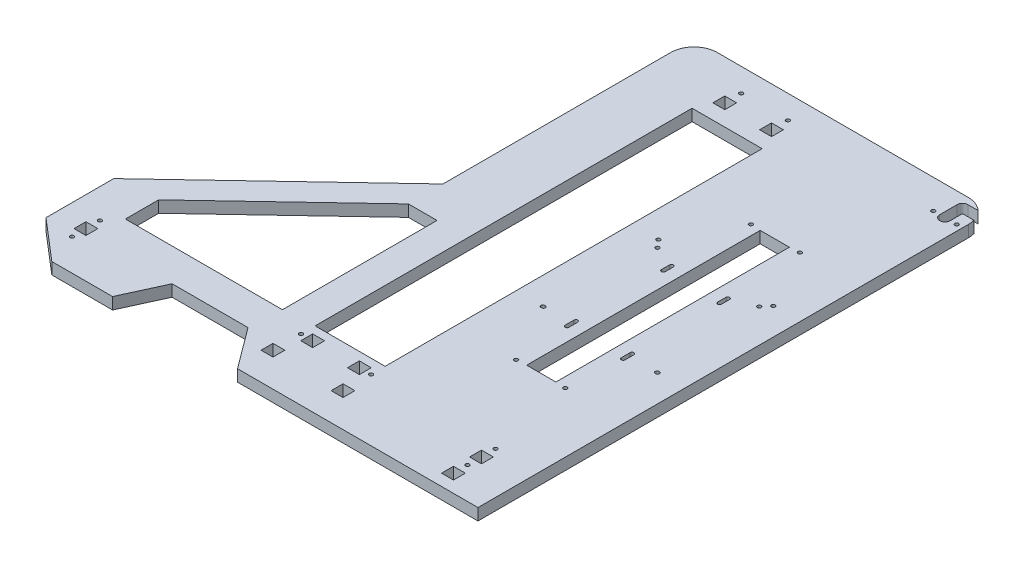
SolidWorks part; units mm, degrees
ref_plane "Front Plane" through (0, 0, 0) normal (0, 0, 1) x (1, 0, 0)
ref_plane "Top Plane" through (0, 0, 0) normal (0, 1, 0) x (1, 0, 0)
ref_plane "Right Plane" through (0, 0, 0) normal (1, 0, 0) x (0, 0, -1)
sketch "Sketch1" plane through (0, 0, 0) normal (0, 1, 0) x (1, 0, 0)
  line L0 (0, 0) -> (-235, 0)
  line L1 (-235, 0) -> (-235, -215)
  line L2 (-235, -215) -> (-380, -352)
  line L3 (-380, -352) -> (-380, -410)
  line L4 (-380, -410) -> (-345, -440)
  line L5 (-345, -440) -> (-293, -440)
  line L6 (-293, -440) -> (-277, -405)
  line L7 (-277, -405) -> (-212, -405)
  line L8 (-212, -405) -> (-185.9255, -440)
  line L9 (-185.9255, -440) -> (0, -440)
  line L10 (0, 0) -> (0, -440)
  line L12 (-293, -440) -> (-185.9255, -440) construction
  dimension "D3" = 235
  dimension "D5" = 58
  dimension "D13" = 190
  dimension "D7" = 35
  dimension "D2" = 126.686
  dimension "D11" = 65
  dimension "D15" = 52
  dimension "D12" = 30
  dimension "D10" = 35
  dimension "D14" = 16
  dimension "D6" = 380
  dimension "D4" = 440
extrude "Boss-Extrude1" add sketch "Sketch1" along normal blind 10
sketch "Sketch16" plane through (0, 10, 0) normal (0, 1, 0) x (1, 0, 0)
  line L0 (0, -440) -> (20, -440)
  line L1 (20, -440) -> (20, 0)
  line L2 (20, 0) -> (0, 0)
  line L3 (0, 0) -> (0, -440)
  dimension "D1" = 20
  dimension "D2" = 90
extrude "Boss-Extrude2" add sketch "Sketch16" against normal through all
sketch "Sketch2" plane through (0, 10, 0) normal (0, 1, 0) x (1, 0, 0)
  line L0 (-235, -215) -> (-235, -405) construction
  line L1 (-277, -405) -> (-212, -405) construction
  line L2 (-345, -440) -> (-345, -318.931) construction
  line L3 (-235, -215) -> (-380, -352) construction
  line L4 (-345, -348.5097) -> (-235, -244.5787)
  line L5 (-235, -244.5787) -> (-210.5, -244.5787)
  line L6 (-210.5, -244.5787) -> (-210.5, -377)
  line L7 (-210.5, -377) -> (-345, -377)
  line L8 (-345, -377) -> (-345, -348.5097)
  line L9 (0, -440) -> (0, 0) construction
  line L10 (-184.5, -375) -> (-124.5, -375)
  line L11 (-184.5, -375) -> (-184.5, -52.1)
  line L12 (-184.5, -52.1) -> (-124.5, -52.1)
  line L13 (-124.5, -375) -> (-124.5, -52.1)
  line L14 (-124.5, -387.1) -> (-184.5, -387.1) construction
  line L15 (-16, -440) -> (-16, 0) construction
  line L16 (20, 0) -> (-235, 0) construction
  line L17 (-354.8, -431.6) -> (-354.8, -328.1903) construction
  line L18 (-21.1, -430.1) -> (-10.9, -430.1)
  line L19 (-21.1, -430.1) -> (-21.1, -419.9)
  line L20 (-21.1, -419.9) -> (-10.9, -419.9)
  line L21 (-10.9, -430.1) -> (-10.9, -419.9)
  line L22 (-21.1, -430.1) -> (-10.9, -419.9) construction
  line L23 (-21.1, -419.9) -> (-10.9, -430.1) construction
  line L24 (-21.1, -406.1) -> (-10.9, -406.1)
  line L25 (-21.1, -406.1) -> (-21.1, -395.9)
  line L26 (-21.1, -395.9) -> (-10.9, -395.9)
  line L27 (-10.9, -406.1) -> (-10.9, -395.9)
  line L28 (-21.1, -406.1) -> (-10.9, -395.9) construction
  line L29 (-21.1, -395.9) -> (-10.9, -406.1) construction
  line L30 (-380, -410) -> (-345, -440) construction
  line L32 (-349.7, -395.9) -> (-359.9, -395.9)
  line L33 (-349.7, -395.9) -> (-349.7, -406.1)
  line L34 (-349.7, -406.1) -> (-359.9, -406.1)
  line L35 (-359.9, -395.9) -> (-359.9, -406.1)
  line L36 (-349.7, -395.9) -> (-359.9, -406.1) construction
  line L37 (-349.7, -406.1) -> (-359.9, -395.9) construction
  line L38 (-185.9255, -440) -> (20, -440) construction
  line L39 (-185.9255, -440) -> (20, -440) construction
  line L40 (-173.924, -34.1) -> (-113.924, -34.1) construction
  line L41 (-154.5, -52.1) -> (-154.5, -34.1) construction
  line L42 (-179.6, -29) -> (-169.4, -29)
  line L43 (-179.6, -29) -> (-179.6, -39.2)
  line L44 (-179.6, -39.2) -> (-169.4, -39.2)
  line L45 (-169.4, -29) -> (-169.4, -39.2)
  line L46 (-179.6, -29) -> (-169.4, -39.2) construction
  line L47 (-179.6, -39.2) -> (-169.4, -29) construction
  line L48 (-129.4, -39.2) -> (-139.6, -29) construction
  line L49 (-129.4, -29) -> (-139.6, -39.2) construction
  line L50 (-139.6, -29) -> (-139.6, -39.2)
  line L51 (-129.4, -39.2) -> (-139.6, -39.2)
  line L52 (-129.4, -29) -> (-129.4, -39.2)
  line L53 (-129.4, -29) -> (-139.6, -29)
  line L54 (-174.5, -34.1) -> (-174.5, -20.1) construction
  line L55 (-134.5, -34.1) -> (-134.5, -20.1) construction
  line L56 (-154.5, -375) -> (-154.5, -440) construction
  line L57 (-174.5, -387.1) -> (-134.5, -387.1) construction
  line L58 (-129.4, -392.2) -> (-139.6, -382) construction
  line L59 (-179.6, -382) -> (-169.4, -382)
  line L60 (-179.6, -382) -> (-179.6, -392.2)
  line L61 (-179.6, -392.2) -> (-169.4, -392.2)
  line L62 (-169.4, -382) -> (-169.4, -392.2)
  line L63 (-179.6, -382) -> (-169.4, -392.2) construction
  line L64 (-179.6, -392.2) -> (-169.4, -382) construction
  line L65 (-129.4, -382) -> (-139.6, -392.2) construction
  line L66 (-139.6, -382) -> (-139.6, -392.2)
  line L67 (-129.4, -392.2) -> (-139.6, -392.2)
  line L68 (-129.4, -382) -> (-129.4, -392.2)
  line L69 (-129.4, -382) -> (-139.6, -382)
  line L70 (-119.4, -416.2) -> (-129.6, -406) construction
  line L71 (-189.6, -406) -> (-179.4, -406)
  line L72 (-189.6, -406) -> (-189.6, -416.2)
  line L73 (-189.6, -416.2) -> (-179.4, -416.2)
  line L74 (-179.4, -406) -> (-179.4, -416.2)
  line L75 (-189.6, -406) -> (-179.4, -416.2) construction
  line L76 (-189.6, -416.2) -> (-179.4, -406) construction
  line L77 (-119.4, -406) -> (-129.6, -416.2) construction
  line L78 (-129.6, -406) -> (-129.6, -416.2)
  line L79 (-119.4, -416.2) -> (-129.6, -416.2)
  line L80 (-119.4, -406) -> (-119.4, -416.2)
  line L81 (-119.4, -406) -> (-129.6, -406)
  line L82 (-359.9, -395.9) -> (-10.9, -395.9) construction
  circle A0 centre (-16, -413) radius 1.6
  circle A1 centre (-16, -389) radius 1.6
  circle A2 centre (-354.8, -413) radius 1.6
  circle A3 centre (-354.8, -389) radius 1.6
  circle A4 centre (-174.5, -20.1) radius 1.6
  circle A5 centre (-134.5, -20.1) radius 1.6
  circle A6 centre (-124.5, -387.1) radius 1.6
  circle A7 centre (-184.5, -387.1) radius 1.6
  point P25 (-16, -425)
  point P30 (-16, -401)
  point P44 (-354.8, -401)
  point P61 (-174.5, -34.1)
  point P72 (-134.5, -34.1)
  point P85 (-174.5, -387.1)
  point P94 (-134.5, -387.1)
  point P95 (-184.5, -411.1)
  point P104 (-124.5, -411.1)
  point P105 (-154.5, -387.1)
  dimension "D13" = 3.2
  dimension "D14" = 3.2
  dimension "D23" = 3.2
  dimension "D24" = 3.2
  dimension "D31" = 3.2
  dimension "D37" = 3.2
  dimension "D1" = 21.5
  dimension "D2" = 28
  dimension "D3" = 24.5
  dimension "D4" = 60
  dimension "D7" = 26
  dimension "D8" = 10.2
  dimension "D9" = 10.2
  dimension "D10" = 10.2
  dimension "D11" = 10.2
  dimension "D12" = 24
  dimension "D15" = 24
  dimension "D19" = 10.2
  dimension "D20" = 10.2
  dimension "D26" = 12
  dimension "D27" = 10.2
  dimension "D28" = 10.2
  dimension "D33" = 10.2
  dimension "D38" = 10.2
  dimension "D39" = 10.2
  dimension "D41" = 24
  dimension "D34" = 30
  dimension "D36" = 12.1
  dimension "D30" = 18
  dimension "D29" = 40
  dimension "D17" = 15
  dimension "D32" = 14
  dimension "D35" = 20
  dimension "D16" = 12
  dimension "D21" = 90
  dimension "D25" = 24
  dimension "D5" = 353
  dimension "D22" = 349
  dimension "D40" = 30
  dimension "D6" = 65
  dimension "D42" = 0
  dimension "D43" = 0
  dimension "D18" = 16
extrude "Cut-Extrude1" cut sketch "Sketch2" against normal through all
fillet "Fillet1" radius 20 2 edges at (-235, 5, 0) (20, 5, 0)
sketch "Sketch11" [suppressed] plane through (0, 10, 0) normal (0, 1, 0) x (1, 0, 0)
  line L0 (-124.5, -213.55) -> (20, -213.55) construction
  line L1 (20, -440) -> (20, -20) construction
  line L3 (-52.25, -213.55) -> (-52.25, -440) construction
  line L6 (-124.5, -375) -> (-124.5, -52.1) construction
  line L8 (-185.9255, -440) -> (20, -440) construction
  circle A0 centre (-52.25, -413) radius 12.5
  circle A1 centre (-16, -413) radius 1.6 construction
  dimension "D1" = 25
  dimension "D2" = 0
  dimension "D3" = 0
extrude "WiringHole" [suppressed] cut sketch "Sketch11" against normal through all
sketch "Sketch9" [suppressed] plane through (0, 10, 0) normal (0, 1, 0) x (1, 0, 0)
  line L0 (-52.25, -400.5) -> (-52.25, 0) construction
  line L1 (0, 0) -> (-215, 0) construction
  line L2 (-124.5, -213.55) -> (20, -213.55) construction
  line L3 (-124.5, -375) -> (-124.5, -52.1) construction
  line L4 (-4.75, -125.05) -> (-4.75, -302.05) construction
  line L6 (-99.75, -125.05) -> (-4.75, -125.05) construction
  line L7 (-4.75, -302.05) -> (-99.75, -302.05) construction
  line L8 (-99.75, -302.05) -> (-99.75, -125.05) construction
  line L9 (20, -440) -> (20, -20) construction
  circle A0 centre (-52.25, -413) radius 12.5 construction
  circle A1 centre (-99.75, -125.05) radius 1.6
  circle A2 centre (-4.75, -125.05) radius 1.6
  circle A3 centre (-4.75, -302.05) radius 1.6
  circle A4 centre (-99.75, -302.05) radius 1.6
  dimension "D3" = 3.2
  dimension "D4" = 3.2
  dimension "D1" = 95
  dimension "D2" = 177
  dimension "D5" = 47.5
extrude "MountingHoles-PSU" [suppressed] cut sketch "Sketch9" against normal through all
sketch "Sketch10" plane through (0, 10, 0) normal (0, 1, 0) x (1, 0, 0)
  line L0 (-124.5, -213.55) -> (20, -213.55) construction
  line L1 (20, -440) -> (20, -20) construction
  line L3 (-52.25, -213.55) -> (-52.25, 0) construction
  line L7 (-124.5, -375) -> (-124.5, -52.1) construction
  line L8 (-64.75, -313.55) -> (-39.75, -313.55)
  line L9 (-64.75, -313.55) -> (-64.75, -113.55)
  line L10 (-64.75, -113.55) -> (-39.75, -113.55)
  line L11 (-39.75, -313.55) -> (-39.75, -113.55)
  line L12 (-64.75, -313.55) -> (-39.75, -113.55) construction
  line L13 (-64.75, -113.55) -> (-39.75, -313.55) construction
  line L15 (0, 0) -> (-215, 0) construction
  line L17 (-52.25, -213.55) -> (-52.25, -440) construction
  line L18 (-185.9255, -440) -> (20, -440) construction
  line L19 (-64.75, -213.55) -> (-39.75, -213.55) construction
  line L20 (-52.25, -313.55) -> (-52.25, -113.55) construction
  dimension "D1" = 25
  dimension "D2" = 200
  dimension "D3" = 0
  dimension "D4" = 0
  dimension "D5" = 0
extrude "WiringSlot" cut sketch "Sketch10" against normal through all
sketch "CenterLines" plane through (0, 10, 0) normal (0, 1, 0) x (1, 0, 0)
  line L0 (-52.25, -313.55) -> (-52.25, -113.55) construction
  line L1 (-64.75, -313.55) -> (-39.75, -313.55) construction
  line L2 (-39.75, -113.55) -> (-64.75, -113.55) construction
  line L3 (-64.75, -213.55) -> (-39.75, -213.55) construction
  line L4 (-64.75, -113.55) -> (-64.75, -313.55) construction
  line L5 (-39.75, -313.55) -> (-39.75, -113.55) construction
ref_plane "Plane1" through (-52.25, 0, 0) normal (1, 0, 0) x (0, 0, -1)
sketch "Sketch6" plane through (0, 10, 0) normal (0, 1, 0) x (1, 0, 0)
  line L0 (-52.25, -313.55) -> (-52.25, -113.55) construction
  line L1 (-76.35, -222.4) -> (-28.15, -222.4) construction
  line L2 (-28.15, -177.95) -> (-28.15, -260.45) construction
  line L3 (-64.75, -313.55) -> (-39.75, -313.55) construction
  line L4 (-64.75, -231.25) -> (-39.75, -231.25) construction
  line L5 (-39.75, -113.55) -> (-64.75, -113.55) construction
  line L6 (-28.15, -177.95) -> (-28.15, -184.95) construction
  line L7 (-26.55, -177.95) -> (-26.55, -184.95)
  line L8 (-29.75, -177.95) -> (-29.75, -184.95)
  line L9 (-64.75, -213.55) -> (-39.75, -213.55) construction
  line L10 (-64.75, -113.55) -> (-64.75, -313.55) construction
  line L11 (-39.75, -313.55) -> (-39.75, -113.55) construction
  line L12 (-28.15, -267.45) -> (-28.15, -260.45) construction
  line L13 (-29.75, -267.45) -> (-29.75, -260.45)
  line L14 (-76.35, -259.85) -> (-76.35, -184.95) construction
  line L15 (-28.15, -267.45) -> (-28.15, -184.95) construction
  line L16 (-26.55, -267.45) -> (-26.55, -260.45)
  arc A2 (-26.55, -177.95) -> (-29.75, -177.95) centre (-28.15, -177.95) ccw
  arc A3 (-29.75, -184.95) -> (-26.55, -184.95) centre (-28.15, -184.95) ccw
  circle A4 centre (-76.35, -259.85) radius 1.6
  circle A6 centre (-76.35, -184.95) radius 1.6
  arc A8 (-29.75, -267.45) -> (-26.55, -267.45) centre (-28.15, -267.45) ccw
  arc A9 (-26.55, -260.45) -> (-29.75, -260.45) centre (-28.15, -260.45) ccw
  point P20 (-28.15, -181.45)
  point P25 (-28.15, -263.95)
  dimension "D8" = 3.2
  dimension "D12" = 3.2
  dimension "D4" = 1.6
  dimension "D5" = 1.6
  dimension "D11" = 82.5
  dimension "D14" = 74.9
  dimension "D2" = 24.1
  dimension "D3" = 48.2
  dimension "D6" = 8.85
  dimension "D9" = 7
  dimension "D10" = 7
extrude "MountingHoles-RAMPS" cut sketch "Sketch6" against normal through all
mirror "Mirror1" about plane through (-52.25, 0, 0) normal (1, 0, 0) of "MountingHoles-RAMPS"
sketch "Sketch5" plane through (0, 10, 0) normal (0, 1, 0) x (1, 0, 0)
  line L0 (-39.75, -213.55) -> (-64.75, -213.55) construction
  line L3 (-39.75, -313.55) -> (-39.75, -113.55) construction
  line L5 (-64.75, -113.55) -> (-64.75, -313.55) construction
  line L7 (-31.25, -113.05) -> (-73.25, -113.05) construction
  line L8 (-31.25, -314.05) -> (-73.25, -314.05) construction
  line L9 (-52.25, -213.55) -> (-52.25, -113.05) construction
  line L10 (-52.25, -213.55) -> (-52.25, -314.05) construction
  circle A0 centre (-73.25, -113.05) radius 1.6
  circle A1 centre (-31.25, -113.05) radius 1.6
  circle A2 centre (-31.25, -314.05) radius 1.6
  circle A3 centre (-73.25, -314.05) radius 1.6
  point P17 (-52.25, -113.05)
  point P22 (-52.25, -314.05)
  dimension "D2" = 3.2
  dimension "D5" = 3.2
  dimension "D6" = 3.2
  dimension "D7" = 3.2
  dimension "D3" = 201
  dimension "D4" = 100.5
  dimension "D8" = 21
  dimension "D9" = 21
  dimension "D10" = 100.5
extrude "MountingHoles-Melzi" cut sketch "Sketch5" against normal through all
sketch "Sketch13" plane through (0, 0, 0) normal (0, -1, 0) x (-1, 0, 0)
  line L0 (64.75, -213.55) -> (124.5, -213.55) construction
  line L1 (124.5, -375) -> (124.5, -52.1) construction
  line L2 (101.46, -263.065) -> (101.46, -164.035) construction
  line L3 (52.25, -313.55) -> (52.25, -113.55) construction
  line L6 (101.46, -263.065) -> (3.56, -263.065) construction
  circle A0 centre (101.46, -164.035) radius 1.6
  circle A1 centre (101.46, -263.065) radius 1.6
  circle A2 centre (8.62, -170.515) radius 1.6
  circle A3 centre (3.56, -263.065) radius 1.6
  point P11 (101.46, -213.55)
  dimension "D1" = 3.2
  dimension "D6" = 3.2
  dimension "D8" = 3.2
  dimension "D2" = 49.515
  dimension "D3" = 49.21
  dimension "D4" = 6.48
  dimension "D5" = 92.84
  dimension "D7" = 97.9
extrude "Mountingholes-Smoothieboard" cut sketch "Sketch13" against normal through all
mirror "Flipped" about plane through (-52.25, 0, 0) normal (1, 0, 0) of "Mountingholes-Smoothieboard"
sketch "Sketch17" plane through (0, 10, 0) normal (0, 1, 0) x (1, 0, 0)
  line L0 (0, 0) -> (20, 0) construction
  line L1 (20, -23.6361) -> (20, 0) construction
  line L2 (20, -440) -> (20, -20) construction
  line L3 (20, -10) -> (5, -10) construction
  line L4 (20, -14.5) -> (5, -14.5)
  line L5 (20, -5.5) -> (5, -5.5)
  arc A0 (20, -14.5) -> (20, -5.5) centre (20, -10) ccw
  arc A1 (5, -5.5) -> (5, -14.5) centre (5, -10) ccw
  point P8 (12.5, -10)
  dimension "D1" = 9
  dimension "D2" = 15
  dimension "D3" = 10
extrude "Cut-Extrude3" cut sketch "Sketch17" against normal through all
sketch "Sketch18" plane through (0, 10, 0) normal (0, 1, 0) x (1, 0, 0)
  line L0 (5, -5.5) -> (5, -14.5) construction
  line L1 (0.5, -10) -> (5, -10) construction
  line L2 (5, -10) -> (5, -25) construction
  line L3 (9.5, -10) -> (9.5, -25)
  line L4 (0.5, -10) -> (0.5, -25)
  arc A0 (5, -5.5) -> (5, -14.5) centre (5, -10) ccw construction
  arc A1 (9.5, -10) -> (0.5, -10) centre (5, -10) ccw
  arc A2 (0.5, -25) -> (9.5, -25) centre (5, -25) ccw
  point P10 (5, -17.5)
  dimension "D1" = 9
  dimension "D2" = 0
  dimension "D3" = 15
extrude "Cut-Extrude4" cut sketch "Sketch18" against normal through all
sketch "Sketch19" plane through (0, 10, 0) normal (0, 1, 0) x (1, 0, 0)
  line L0 (-5, -25) -> (15, -25) construction
  line L1 (5, -25) -> (5, -5.5) construction
  circle A0 centre (15, -25) radius 1.6
  arc A1 (5, -5.5) -> (0.5, -10) centre (5, -10) ccw construction
  circle A2 centre (-5, -25) radius 1.6
  dimension "D2" = 3.2
extrude "Cut-Extrude5" cut sketch "Sketch19" against normal through all
sketch "Sketch20" plane through (0, 10, 0) normal (0, 1, 0) x (1, 0, 0)
equation "\"Y-ROD-SPACING\"=75"
equation "\"Y-BED-OFFSET\"=2"
equation "\"Y-BED-ROD-INSET\"=3.5"
equation "\"T-SLOT-NUT-FILLET-RADIUS\"=0.25"
equation "\"T-SLOT-SCREW-SHAFT-RADIUS\"=1.75"
equation "\"T-SLOT-SCREW-SHAFT-CUTOUT-LENGTH\"=10.5"
equation "\"T-SLOT-NUT-DEPTH\"=4.2"
equation "\"T-SLOT-NUT-WIDTH\"=3"
equation "\"T-SLOT-NUT-END-DISTANCE\"=8"
equation "\"ACRYLIC-TAB-CUTOUT-SIZE\"=\"ACRYLIC-THICKNESS\"+\"ACRYLIC-TAB-TOLERANCE\"*2"
equation "\"ACRYLIC-TAB-WIDTH\"=\"ACRYLIC-THICKNESS\""
equation "\"ACRYLIC-M3-HOLE\"=3.2"
equation "\"SMOOTHROD-CAP-SCREW-DISTANCE\"=20"
equation "\"FRAME-WIDTH-INNER\"=370"
equation "\"D24@Sketch2\"=\"ACRYLIC-M3-HOLE\""
equation "\"D23@Sketch2\"=\"ACRYLIC-M3-HOLE\""
equation "\"D19@Sketch2\"=\"ACRYLIC-THICKNESS\"+\"ACRYLIC-TAB-TOLERANCE\"*2"
equation "\"D20@Sketch2\"=\"ACRYLIC-TAB-WIDTH\"+\"ACRYLIC-TAB-TOLERANCE\"*2"
equation "\"D37@Sketch2\"=\"ACRYLIC-M3-HOLE\""
equation "\"D33@Sketch2\"=\"ACRYLIC-TAB-CUTOUT-SIZE\""
equation "\"D38@Sketch2\"=\"ACRYLIC-TAB-CUTOUT-SIZE\""
equation "\"D39@Sketch2\"=\"ACRYLIC-TAB-CUTOUT-SIZE\""
equation "\"D13@Sketch2\"=\"ACRYLIC-M3-HOLE\""
equation "\"D14@Sketch2\"=\"ACRYLIC-M3-HOLE\""
equation "\"D8@Sketch2\"=\"ACRYLIC-TAB-CUTOUT-SIZE\""
equation "\"D9@Sketch2\"=\"ACRYLIC-TAB-CUTOUT-SIZE\""
equation "\"D10@Sketch2\"=\"ACRYLIC-TAB-CUTOUT-SIZE\""
equation "\"D11@Sketch2\"=\"ACRYLIC-TAB-CUTOUT-SIZE\""
equation "\"D31@Sketch2\"=\"ACRYLIC-M3-HOLE\""
equation "\"D27@Sketch2\"=\"ACRYLIC-THICKNESS\"+\"ACRYLIC-TAB-TOLERANCE\"*2"
equation "\"D28@Sketch2\"=\"ACRYLIC-TAB-WIDTH\"+\"ACRYLIC-TAB-TOLERANCE\"*2"
equation "\"NEMA17-HOLE-SPACING\"=31"
equation "\"NEMA17-CENTRAL-CUTOUT\"=22.5"
equation "\"Z-BRACKET-REACH\"=55"
equation "\"TOP-BRACKET-SPACING\"=40"
equation "\"D29@Sketch2\"=\"TOP-BRACKET-SPACING\""
equation "\"ACRYLIC-THICKNESS\"=10"
equation "\"SMOOTHROD-Z-LENGTH\"=350"
equation "\"D5@Sketch2\"=\"SMOOTHROD-Z-LENGTH\"-\"SMOOTHROD-TIGHTENING-HEADROOM\"+4"
equation "\"SMOOTHROD-X-LENGTH\"=350"
equation "\"SMOOTHROD-Y-LENGTH\"=350"
equation "\"D22@Sketch2\"=\"SMOOTHROD-Y-LENGTH\"-\"SMOOTHROD-TIGHTENING-HEADROOM\""
equation "\"SMOOTHROD-TIGHTENING-HEADROOM\"=1"
equation "\"X-ROD-SPACING\"=45"
equation "\"Z-ROD-SPACING\"=17.5"
equation "\"LEADSCREW-Z-LENGTH\"=300"
equation "\"SCREW-HEAD-RADIUS\"=6"
equation "\"PRINTED-X-SMOOTHROD-DIAMETER\"=8.2"
equation "\"PRINTED-X-SMOOTHROD-CUTOUT\"=10"
equation "\"PRINTED-X-BASE-HEIGHT\"=10"
equation "\"PRINTED-LM8UU-CUTOUT-SIZE\"=16"
equation "\"PRINTED-LM8UU-CUTOUT-LENGTH\"=24.5"
equation "\"PRINTED-X-IDLER-HEIGHT\"=16"
equation "\"PSU-MOUNTING-WIDTH\"=95"
equation "\"PSU-MOUNTING-HEIGHT\"=177"
equation "\"D1@Sketch9\"=\"PSU-MOUNTING-WIDTH\""
equation "\"D3@Sketch9\"=\"ACRYLIC-M3-HOLE\""
equation "\"D1@Boss-Extrude1\"=\"ACRYLIC-THICKNESS\""
equation "\"D6@Sketch1\"=\"SMOOTHROD-Y-LENGTH\"+30"
equation "\"D4@Sketch9\"=\"ACRYLIC-M3-HOLE\""
equation "\"D2@Sketch9\"=\"PSU-MOUNTING-HEIGHT\""
equation "\"D5@Sketch9\"=\"PSU-MOUNTING-WIDTH\"/2"
equation "\"D4@Sketch1\"=\"SMOOTHROD-Z-LENGTH\"+90"
equation "\"D8@Sketch6\"=\"ACRYLIC-M3-HOLE\""
equation "\"D12@Sketch6\"=\"ACRYLIC-M3-HOLE\""
equation "\"D2@Sketch5\"=\"ACRYLIC-M3-HOLE\""
equation "\"D5@Sketch5\"=\"ACRYLIC-M3-HOLE\""
equation "\"D6@Sketch5\"=\"ACRYLIC-M3-HOLE\""
equation "\"D7@Sketch5\"=\"ACRYLIC-M3-HOLE\""
equation "\"D1@Sketch13\"=\"ACRYLIC-M3-HOLE\""
equation "\"D6@Sketch13\"=\"ACRYLIC-M3-HOLE\""
equation "\"D8@Sketch13\"=\"ACRYLIC-M3-HOLE\""
equation "\"D4@Sketch6\"=\"ACRYLIC-M3-HOLE\"/2"
equation "\"D5@Sketch6\"=\"ACRYLIC-M3-HOLE\"/2"
equation "\"Y-BED-SCREW-SPACING\"=209"
equation "\"Y-BED-SCREW-CUTOUT-SLOT-HEIGHT\"=1"
equation "\"ACRYLIC-THICKNESS2\"=4.5"
equation "\"ACRYLIC-TAB-TOLERANCE\"=.1"
equation "\"Z-ROD-INSET\"=16"
equation "\"SCREW-LENGTH-FRAME\"=\"ACRYLIC-THICKNESS\" + 10"
equation "\"SCREW-LENGTH-MOTOR\"=\"ACRYLIC-THICKNESS\" + 5"
equation "\"SCREW-LENGTH-EXTRUDER\"=28"
equation "\"Y-BELT-TO-ROD-DISTANCE\"=20"
equation "\"SPOOL-HOLDER-ROD-SPACING\"=150"
equation "\"ACRYLIC-X-CARRIAGE-WIDTH\"=55"
equation "\"ACRYLIC-X-CARRIAGE-HEIGHT\"=75"
equation "\"ACRYLIC-X-CARRIAGE-LM8UU-CUTOUT-WIDTH\"=24.25"
equation "\"ACRYLIC-X-CARRIAGE-SCREW-SPACING-X\"=15"
equation "\"ACRYLIC-X-CARRIAGE-SCREW-SPACING-Y\"=33"
equation "\"ACRYLIC-X-CARRIAGE-CENTER-TAB-SPACING\"=14"
equation "\"ACRYLIC-X-CARRIAGE-EXTRUDER-OFFSET\"=26"
equation "\"ACRYLIC-X-CARRIAGE-EXTRUDER-ANGLE\"=90"
equation "\"ACRYLIC-X-CARRIAGE-EXTRUDER-SHELF-DEPTH\"=\"ACRYLIC-X-CARRIAGE-EXTRUDER-OFFSET\" + 30"
equation "\"ACRYLIC-X-CARRIAGE-EXTRUDER-BRACE-SPACING\"=23"
equation "\"ACRYLIC-X-CARRIAGE-EXTRUDER-BRACE-TAB-OFFSET\"=20"
equation "\"ACRYLIC-X-CARRIAGE-EXTRUDER-BRACE-HEIGHT\"=35"
equation "\"ACRYLIC-X-CARRIAGE-EXTRUDER-BRACE-SCREW-SPACING\"=22"
equation "\"D1@Sketch19\"=\"SMOOTHROD-CAP-SCREW-DISTANCE\"/2"
equation "\"D2@Sketch19\"=\"ACRYLIC-M3-HOLE\""
